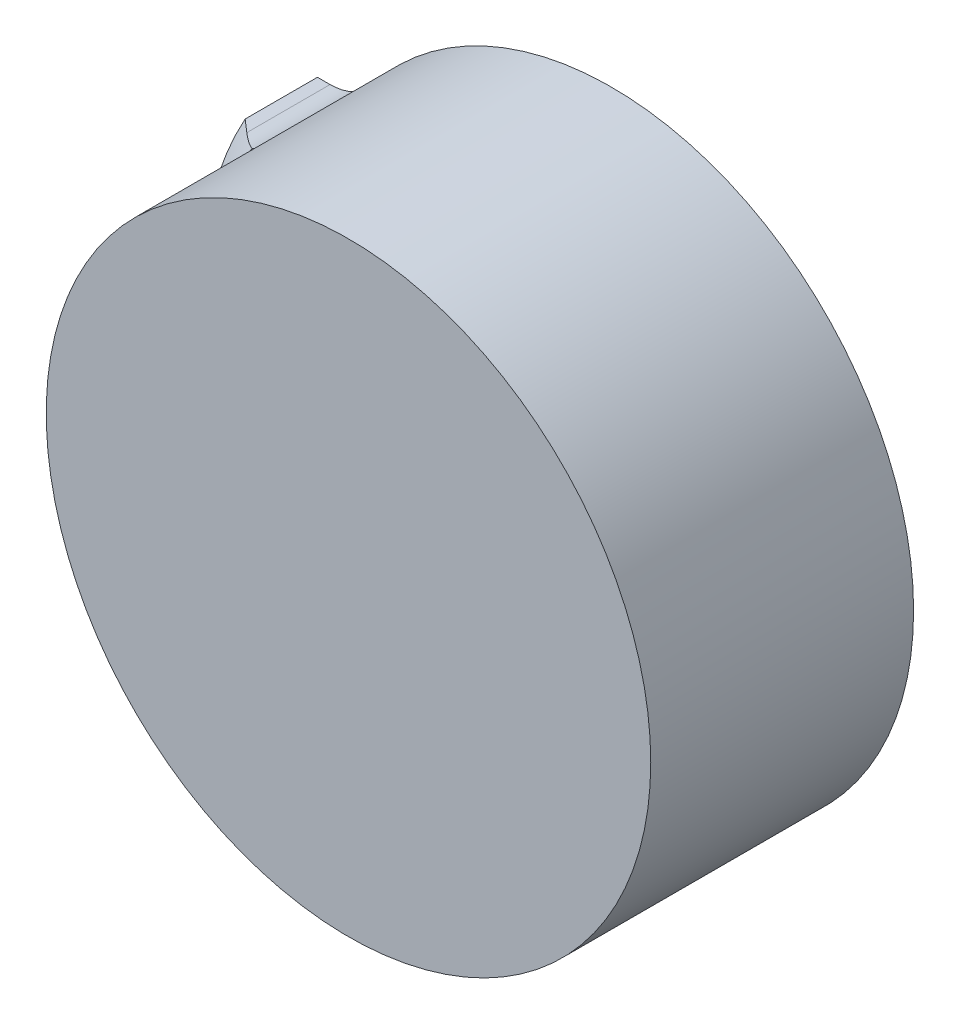
SolidWorks part; units mm, degrees
ref_plane "Спереди" through (0, 0, 0) normal (0, 0, 1) x (1, 0, 0)
ref_plane "Сверху" through (0, 0, 0) normal (0, 1, 0) x (1, 0, 0)
ref_plane "Справа" through (0, 0, 0) normal (1, 0, 0) x (0, 0, -1)
sketch "Эскиз1" plane through (0, 0, 0) normal (0, 0, 1) x (1, 0, 0)
  circle A0 centre (0, 0) radius 23
  dimension "D1" = 46
extrude "Бобышка-Вытянуть1" add sketch "Эскиз1" along normal blind 20
sketch "Эскиз2" plane through (0, 0, 0) normal (0, 0, 1) x (1, 0, 0)
  line L0 (-17.5672, 12.6609) -> (-26.9328, 12.6609) construction
  line L1 (-17.5672, -12.6609) -> (-26.9328, -12.6609) construction
  line L2 (-22.25, 12.6609) -> (-17.5672, 12.6609) construction
  line L3 (-17.5672, 12.6609) -> (-17.5672, -12.6609) construction
  line L4 (-17.5672, -12.6609) -> (-22.25, -12.6609) construction
  line L5 (-22.3626, 12.4609) -> (-17.5672, 12.4609)
  line L6 (-17.5672, -12.4609) -> (-22.3626, -12.4609)
  line L7 (-17.5672, -12.4609) -> (-22.25, -12.4609) construction
  line L8 (-22.25, 12.4609) -> (-17.5672, 12.4609) construction
  line L9 (-17.5672, 12.4609) -> (-17.5672, -12.4609)
  arc A0 (-22.25, 12.6609) -> (-22.25, -12.6609) centre (0, 0) ccw construction
  arc A1 (-22.3626, 12.4609) -> (-22.3626, -12.4609) centre (0, 0) ccw
  dimension "D1" = 0.2
  dimension "D2" = 0.2
extrude "Бобышка-Вытянуть2" add sketch "Эскиз2" along normal blind 7.5
chamfer "Фаска1" distance 2 angle 45 1 edges at (-25.6, 0, 7.5)
fillet "Скругление1" radius 4 2 edges at (-19.332, -12.4609, 3.75) (-19.332, 12.4609, 3.75)
